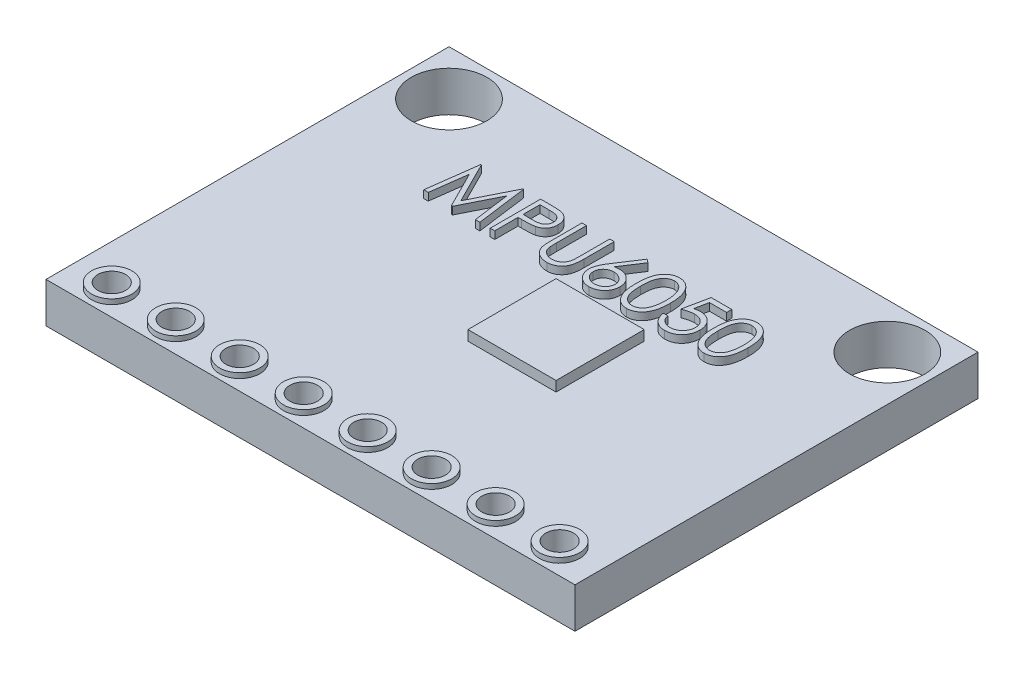
SolidWorks part; units mm, degrees
ref_plane "Front Plane" through (0, 0, 0) normal (0, 0, 1) x (1, 0, 0)
ref_plane "Top Plane" through (0, 0, 0) normal (0, 1, 0) x (1, 0, 0)
ref_plane "Right Plane" through (0, 0, 0) normal (1, 0, 0) x (0, 0, -1)
sketch "Sketch1" plane through (0, 0, 0) normal (0, 1, 0) x (1, 0, 0)
  line L0 (10.5, 16) -> (10.5, 0) construction
  line L1 (0, 0) -> (21, 0)
  line L2 (0, 0) -> (0, 16)
  line L3 (0, 16) -> (21, 16)
  line L4 (21, 0) -> (21, 16)
  line L6 (10.5, 9.75) -> (14, 9.75)
  line L7 (10.5, 9.75) -> (10.5, 6.25)
  line L8 (10.5, 6.25) -> (14, 6.25)
  line L9 (14, 9.75) -> (14, 6.25)
  circle A0 centre (1.61, 1) radius 0.55
  circle A1 centre (4.15, 1) radius 0.55
  circle A2 centre (6.69, 1) radius 0.55
  circle A3 centre (9.23, 1) radius 0.55
  circle A4 centre (11.77, 1) radius 0.55
  circle A5 centre (14.31, 1) radius 0.55
  circle A6 centre (16.85, 1) radius 0.55
  circle A7 centre (19.39, 1) radius 0.55
  circle A8 centre (1.8, 14.2) radius 1.5
  circle A9 centre (19.2, 14.2) radius 1.5
  circle A10 centre (1.61, 1) radius 0.8
  circle A11 centre (4.15, 1) radius 0.8
  circle A12 centre (6.69, 1) radius 0.8
  circle A13 centre (9.23, 1) radius 0.8
  circle A14 centre (11.77, 1) radius 0.8
  circle A15 centre (14.31, 1) radius 0.8
  circle A16 centre (16.85, 1) radius 0.8
  circle A17 centre (19.39, 1) radius 0.8
  dimension "D3" = 1.1
  dimension "D7" = 3
  dimension "D9" = 1.8
  dimension "D13" = 8
  dimension "D14" = 1.6
  dimension "D1" = 16
  dimension "D2" = 21
  dimension "D4" = 1.61
  dimension "D5" = 1
  dimension "D8" = 1.8
  dimension "D10" = 3.5
  dimension "D11" = 3.5
  dimension "D12" = 6.25
  dimension "D6" = 8
extrude "Boss-Extrude1" add sketch "Sketch1" along normal blind 1.6 contours L0 L3 L2 L1 L7 A13 A12 A11 A10 A8 | L3 L0 L6 L9 L8 L1 L4 A9 A14 A15 A16 A17 region at (15.8912, 0, -8.0887) region at (5.4006, 0, -8.0816)
extrude "Boss-Extrude2" add sketch "Sketch1<3>" along normal blind 2 contours L9 L6 L7 L8 region at (12.25, 0, -8)
sketch "Sketch1<3>" plane through (0, 0, 0) normal (0, 1, 0) x (1, 0, 0) same geometry as "Sketch1"
extrude "Boss-Extrude3" add sketch "Sketch1<4>" along normal blind 1.8 contours A10 A0 | A11 A1 | A12 A2 | A13 A3 | A14 A4 | A15 A5 | A16 A6 | A17 A7 region at (0.8326, 0, -1) region at (3.3726, 0, -1) region at (5.9126, 0, -1) region at (8.4526, 0, -1) region at (10.9926, 0, -1) region at (13.5326, 0, -1) region at (16.0726, 0, -1) region at (18.6126, 0, -1)
sketch "Sketch1<4>" plane through (0, 0, 0) normal (0, 1, 0) x (1, 0, 0) same geometry as "Sketch1"
sketch "Sketch3" plane through (0, 1.6, 0) normal (0, 1, 0) x (1, 0, 0)
  text T0 "MPU6050" font "Century Gothic" height 2
extrude "Boss-Extrude4" add sketch "Sketch3" along normal blind 0.3
